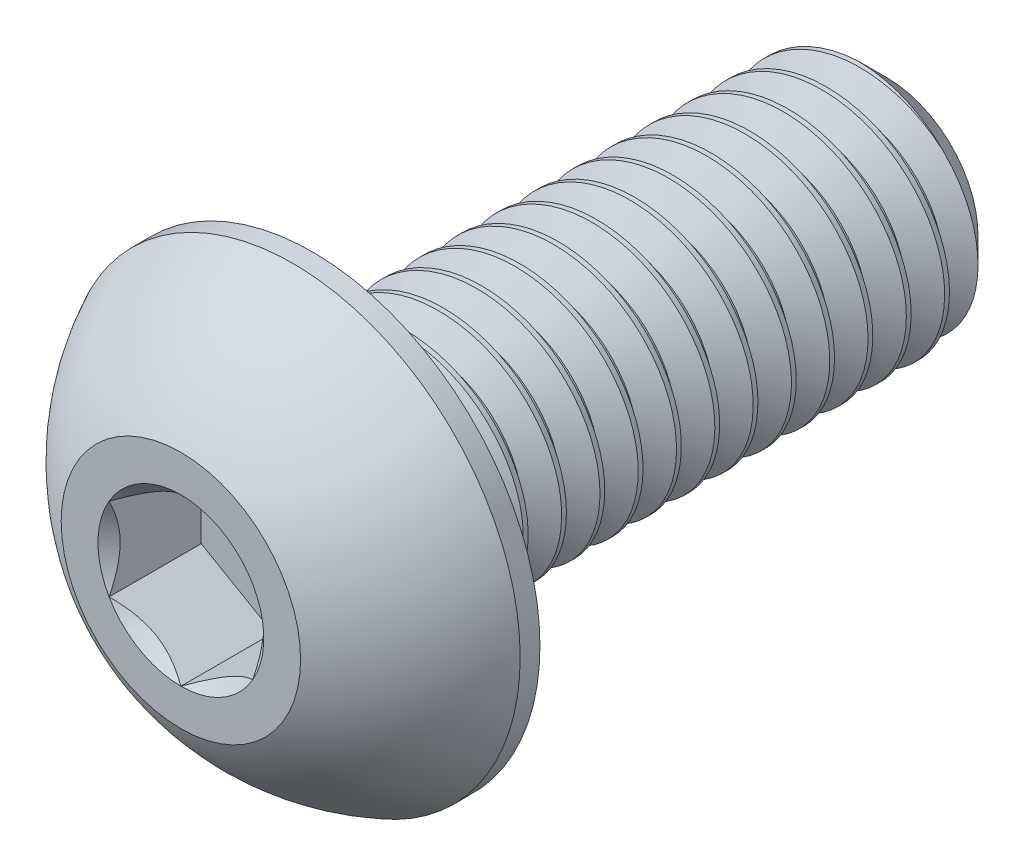
SolidWorks part; units mm, degrees
note: '?' marks a value the reader was unsure of.
ref_plane "Front" through (0, 0, 0) normal (0, 0, 1) x (1, 0, 0)
ref_plane "Top" through (0, 0, 0) normal (0, 1, 0) x (1, 0, 0)
ref_plane "Right" through (0, 0, 0) normal (1, 0, 0) x (0, 0, -1)
sketch "Sketch1" plane through (0, 0, 0) normal (1, 0, 0) x (0, 0, -1)
  line L2 (2.75, 2.5) -> (14.75, 2.5)
  line L3 (14.75, 2.5) -> (14.75, 0)
  line L4 (14.75, 0) -> (2.75, 0)
  line L6 (2.3375, 4.75) -> (2.75, 4.75) construction
  line L7 (14.75, 2.5) -> (14.75, -2.5) construction
  line L8 (0, 0) -> (2.75, 0) construction
  line L9 (2.75, 4.75) -> (2.75, -4.75) construction
  line L11 (2.75, 2.5) -> (2.75, 0)
  line L13 (0, 1.5) -> (0, -1.5) construction
  line L14 (0, 1.5) -> (0, 2.5) construction
  arc A3 (0, 2.5) -> (2.3375, 4.75) centre (4.6581, 0) cw construction
  dimension "D1" = 0.4125
revolve "Revolve1" add sketch "Sketch1" angle 360 mid plane about L4
sketch "Sketch3" plane through (0, 0, -14.75) normal (0, 0, -1) x (-1, 0, 0)
  circle A0 centre (0, 0) radius 2.5
curve "Helix/Spiral1" pitch 0.8 height 12.8 turns 16
chamfer "Chamfer1" distance 0.6 angle 45 1 edges at (0, 2.5, -14.75)
sketch "Sketch7" plane through (0, 0, 0) normal (1, 0, 0) x (0, 0, -1)
  line L6 (2.3375, 4.75) -> (2.75, 4.75) construction
  line L8 (0, 0) -> (2.75, 0) construction
  line L11 (2.75, 4.75) -> (2.75, -4.75) construction
  line L12 (2.3375, 4.75) -> (2.75, 4.75)
  line L13 (0, 0) -> (2.75, 0)
  line L14 (0, 1.5) -> (0, -1.5) construction
  line L15 (2.75, 4.75) -> (2.75, 0)
  line L16 (0, 2.5) -> (0, 0)
  arc A2 (2.3375, 4.75) -> (0, 2.5) centre (4.6581, 0) ccw construction
  arc A3 (2.3375, 4.75) -> (0, 2.5) centre (4.6581, 0) ccw
revolve "Revolve2" add sketch "Sketch7" angle 360 mid plane about L13
sketch "Sketch5" plane through (0, 0, 0) normal (0, 0, 1) x (1, 0, 0)
  line L1 (1.5, -0.866) -> (1.5, 0.866)
  line L2 (1.5, 0.866) -> (0, 1.7321)
  line L3 (0, 1.7321) -> (-1.5, 0.866)
  line L4 (-1.5, 0.866) -> (-1.5, -0.866)
  line L5 (-1.5, -0.866) -> (0, -1.7321)
  line L6 (0, -1.7321) -> (1.5, -0.866)
  circle A0 centre (0, 0) radius 1.5 construction
extrude "Cut-Extrude2" cut sketch "Sketch5" against normal blind 1.925
sketch "Sketch6" plane through (0, 0, 0) normal (0, 0, 1) x (1, 0, 0)
  circle A0 centre (0, 0) radius 1.7321
extrude "Cut-Extrude3" cut sketch "Sketch6" against normal blind 1.925 draft 45
sketch "Sketch2" plane through (0, 0, 0) normal (1, 0, 0) x (0, 0, -1)
  line L0 (14.15, 2.5) -> (14.85, 2.5)
  line L1 (14.85, 2.5) -> (14.55, 1.9804)
  line L2 (14.55, 1.9804) -> (14.45, 1.9804)
  line L3 (14.45, 1.9804) -> (14.15, 2.5)
  line L4 (14.3, 2.2402) -> (14.7, 2.2402) construction
  dimension "D1" = 60
  dimension "D2" = 0.1
  dimension "D3" = 0.4
sweep "Cut-Sweep1" cut profiles "Sketch2" path "Helix/Spiral1"
sketch "Sketch10" plane through (0, 0, 0) normal (1, 0, 0) x (0, 0, -1)
  line L0 (14.75, 2.5) -> (14.75, -2.5) construction
  point P0 (13.55, -2.5)
  dimension "D1" = 1.2
ref_axis "Center Axis 1" through (0, 0, -8.1113) along (0, 0, 1)?
ref_plane "Contact Plane 1" through (0, 0, -2.75) normal (0, 0, -1) x (-1, 0, 0)
ref_plane "Contact Plane 2" through (0, 0, 0) normal (0, 0, 1) x (1, 0, 0)
equation "\"D3@Helix/Spiral1\" = \"Lg@Sketch1\" + \"D4@Helix/Spiral1\""
equation "\"D2@Sketch2\" = \"D4@Helix/Spiral1\" * .125"
equation "\"D3@Sketch2\" = \"D4@Helix/Spiral1\" * .5"
equation "\"D1@Chamfer1\" = \"D4@Helix/Spiral1\" * .75"
equation "\"D1@Cut-Extrude2\" = \"Head Ht@Sketch1\" * .7"
equation "\"D1@Sketch1\" = \"Head Ht@Sketch1\" * .15"
equation "\"D1@Sketch10\" = \"D4@Helix/Spiral1\" * 1.5"
equation "\"D1@Cut-Extrude3\" = \"D1@Cut-Extrude2\""
